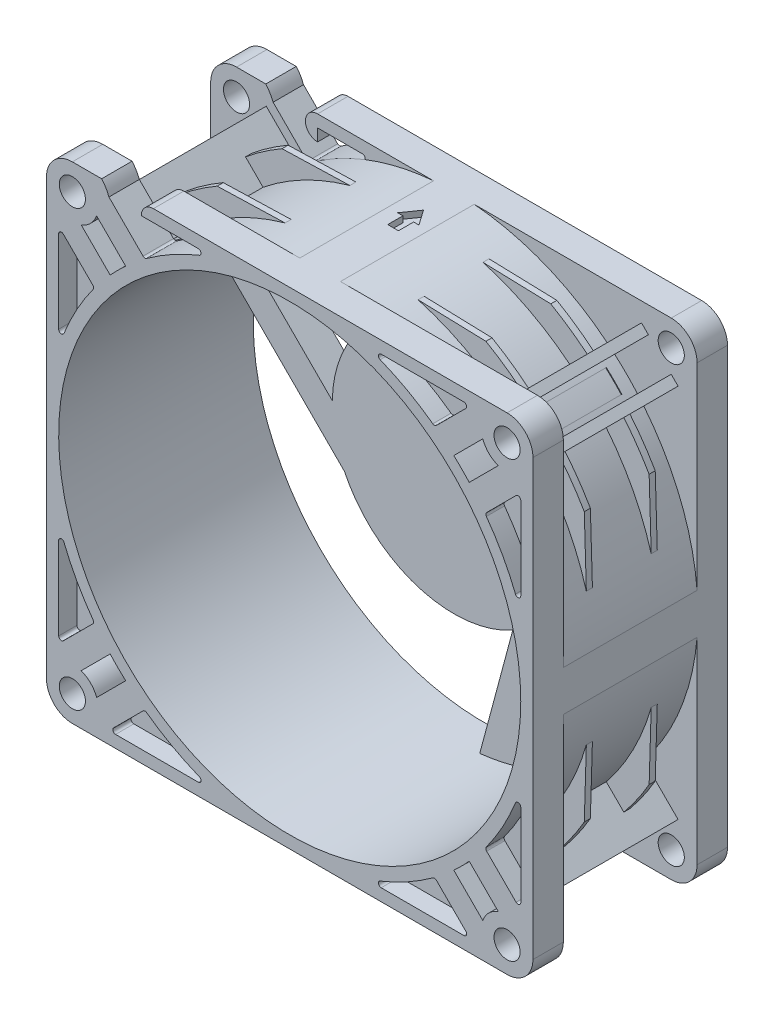
SolidWorks part; units mm, degrees
material "PW100:Mi:0:3:C1:0:1:2:Re:26:"
ref_plane "Front" through (0, 0, 0) normal (0, 0, 1) x (1, 0, 0)
ref_plane "Top" through (0, 0, 0) normal (0, 1, 0) x (1, 0, 0)
ref_plane "Right" through (0, 0, 0) normal (1, 0, 0) x (0, 0, -1)
sketch "Support-Front" plane through (0, 0, 0) normal (0, 0, 1) x (1, 0, 0)
  line L0 (-40, 0) -> (40, 0) construction
  line L1 (0, 40) -> (0, -40) construction
  line L2 (40, -35.75) -> (40, 35.75)
  line L3 (-40, -35.75) -> (-40, 35.75)
  line L4 (35.75, 40) -> (-35.75, 40)
  line L5 (35.75, -40) -> (-35.75, -40)
  line L6 (0, 40) -> (0, 54.8081) construction
  arc A0 (40, 35.75) -> (35.75, 40) centre (35.75, 35.75) ccw
  arc A1 (-40, 35.75) -> (-35.75, 40) centre (-35.75, 35.75) cw
  arc A2 (-40, -35.75) -> (-35.75, -40) centre (-35.75, -35.75) ccw
  arc A3 (40, -35.75) -> (35.75, -40) centre (35.75, -35.75) cw
  circle A4 centre (35.75, 35.75) radius 2.15
  circle A5 centre (-35.75, 35.75) radius 2.15
  circle A6 centre (-35.75, -35.75) radius 2.15
  circle A7 centre (35.75, -35.75) radius 2.15
  circle A8 centre (0, 0) radius 38
  circle A9 centre (0, 0) radius 20
  circle A10 centre (0, 0) radius 40
  circle A11 centre (0, 0) radius 54.8081 construction
  dimension "Diam-Fixing-Hole" = 4.3
  dimension "Diam-Fan-Hole" = 76
  dimension "Diam-Fixing-Plate-Fan" = 40
  dimension "Dist-Fixing-Hole" = 71.5
  dimension "Width" = 80
sketch "Support-Right" plane through (0, 0, 0) normal (1, 0, 0) x (0, 0, -1)
  line L0 (-32, 0) -> (0, 0) construction
  line L1 (-16, 40) -> (-16, -40) construction
  line L2 (-5, 40) -> (-5, -40)
  line L3 (-32, 40) -> (0, 40)
  line L4 (-32, 40) -> (-32, -40)
  line L5 (-32, -40) -> (0, -40)
  line L6 (0, 40) -> (0, -40)
  line L7 (-27, 40) -> (-27, -40)
  line L8 (-16, 40) -> (-16, 40.2793) construction
  line L9 (0, 0) -> (-2.5, 0) construction
  line L10 (-2.5, 0) -> (-5, 0) construction
  line L11 (0, 40.2793) -> (-10.6667, 40.2793) construction
  line L12 (-10.6667, 40.2793) -> (-21.3333, 40.2793) construction
  line L13 (-21.3333, 40.2793) -> (-32, 40.2793) construction
  line L14 (0, 40) -> (-16, 40.2793) construction
  dimension "D1" = 1
  dimension "Thickness" = 32
  dimension "D2" = 22
  dimension "Thickness-Flange" = 5
sketch "Support-Front-Reinforcment-Place" plane through (0, 0, 0) normal (0, 0, 1) x (1, 0, 0)
  line L0 (0, 40) -> (0, 0) construction
  line L1 (0, 38) -> (0, 40) construction
  line L2 (12.612, 40) -> (13.3947, 35.561)
  line L3 (35.75, 40) -> (-35.75, 40) construction
  line L4 (-12.612, 40) -> (-13.3947, 35.561)
  line L5 (12.612, 40) -> (0, 0) construction
  line L6 (-12.612, 40) -> (0, 0) construction
  line L7 (12.612, 40) -> (-12.612, 40)
  circle A3 centre (0, 0) radius 38 construction
  arc A4 (13.3947, 35.561) -> (-13.3947, 35.561) centre (0, 0) ccw
  point P10 (0, 39)
  dimension "D1" = 20
  dimension "D2" = 35
sketch "Support-Front-Reinforcment-Strip" plane through (0, 0, 0) normal (0, 0, 1) x (1, 0, 0)
  line L0 (25.119, 31.1294) -> (32.7448, 38.7552)
  line L1 (31.1294, 25.119) -> (38.7552, 32.7448)
  line L2 (35.75, 35.75) -> (0, 0) construction
  line L3 (29.5285, 26.9827) -> (34.3006, 31.7548)
  line L4 (33.4494, 32.1765) -> (28.9136, 27.6406)
  line L5 (35.7435, 31.9896) -> (30.0989, 26.345)
  line L6 (31.9896, 35.7435) -> (26.345, 30.0989)
  line L7 (35.75, 35.75) -> (30.0989, 26.345) construction
  line L8 (35.75, 35.75) -> (26.345, 30.0989) construction
  line L9 (38, 29.7331) -> (30.6837, 22.4168)
  line L10 (29.7331, 38) -> (22.4168, 30.6837)
  line L11 (38, 29.7331) -> (38, 0)
  line L12 (29.7331, 38) -> (0, 38)
  line L13 (35.7435, 31.9896) -> (36.8718, 30.8613)
  line L14 (31.9896, 35.7435) -> (30.8613, 36.8718)
  line L15 (31.9146, 29.3687) -> (31.2781, 30.0052) construction
  line L16 (29.7331, 38) -> (31.9896, 35.7435) construction
  line L17 (38, 29.7331) -> (36.8718, 30.8613) construction
  line L18 (29.0966, 37.55) -> (28.1965, 37.55) construction
  line L19 (31.2781, 30.0052) -> (30.6417, 30.6417) construction
  line L20 (28.2843, 28.2843) -> (33.4494, 32.1765) construction
  line L21 (32.1765, 33.4494) -> (27.6406, 28.9136)
  line L22 (26.9827, 29.5285) -> (31.7548, 34.3006)
  line L23 (0, 0) -> (-38, 0) construction
  line L24 (0, 0) -> (0, 40) construction
  line L25 (-38, 29.7331) -> (-38, 0)
  line L26 (-38, 29.7331) -> (-30.6837, 22.4168)
  line L27 (-38, 29.7331) -> (-40, 27.7331)
  line L28 (-40, -35.75) -> (-40, 35.75) construction
  line L29 (-38, -29.7331) -> (-40, -27.7331)
  line L30 (-38, -29.7331) -> (-30.6837, -22.4168)
  line L31 (-38, -29.7331) -> (-38, 0)
  line L32 (22.4168, 38) -> (22.4168, 36)
  line L33 (35.75, 40) -> (-35.75, 40) construction
  line L34 (-22.4168, 38) -> (-22.4168, 40) construction
  line L35 (22.4168, 38) -> (22.4168, 40) construction
  line L36 (-22.4168, 38) -> (-22.4168, 36)
  line L37 (0, 38) -> (-22.4168, 38)
  line L38 (-29.7331, 38) -> (-22.4168, 30.6837)
  arc A0 (32.7448, 38.7552) -> (38.7552, 32.7448) centre (35.75, 35.75) cw
  arc A1 (40, 35.75) -> (35.75, 40) centre (35.75, 35.75) ccw construction
  circle A2 centre (0, 0) radius 38
  circle A3 centre (0, 0) radius 40 construction
  arc A4 (22.4168, 36) -> (22.4168, 40) centre (22.4168, 38) ccw
  circle A5 centre (35.75, 35.75) radius 4.25
  arc A6 (31.1294, 25.119) -> (25.119, 31.1294) centre (0, 0) ccw
  circle A7 centre (0, 0) radius 38 construction
  circle A8 centre (28.6466, 37.55) radius 0.45
  circle A9 centre (23.8023, 32.7056) radius 0.45
  circle A10 centre (15.0402, 37.55) radius 0.45
  circle A11 centre (32.7056, 23.8023) radius 0.45
  circle A12 centre (37.55, 15.0402) radius 0.45
  circle A13 centre (37.55, 28.6466) radius 0.45
  circle A14 centre (35.75, 35.75) radius 6.4238
  arc A15 (-22.4168, 36) -> (-22.4168, 40) centre (-22.4168, 38) cw
  circle A16 centre (-35.75, 35.75) radius 6.4238
  circle A17 centre (-28.6466, 37.55) radius 0.45
  circle A18 centre (-23.8023, 32.7056) radius 0.45
  circle A19 centre (-15.0402, 37.55) radius 0.45
  dimension "D1" = 14
  dimension "D2" = 45
  dimension "D3" = 8
sketch "Support-Front-Bone" plane through (0, 0, 0) normal (0, 0, 1) x (1, 0, 0)
  line L0 (-19.6962, -3.473) -> (-35.8291, 12.66) construction
  line L1 (-19.9967, 0.3631) -> (-34.8294, 15.1958)
  line L2 (-18.0123, -8.6923) -> (-36.67, 9.9654)
  line L3 (0, 0) -> (0, 40) construction
  line L4 (35.75, 40) -> (-35.75, 40) construction
  line L6 (0, 0) -> (-19.6962, -3.473) construction
  circle A0 centre (0, 0) radius 38 construction
  circle A1 centre (0, 0) radius 20 construction
  arc A2 (-19.9967, 0.3631) -> (-18.0123, -8.6923) centre (0, 0) ccw
  arc A3 (-34.8294, 15.1958) -> (-36.67, 9.9654) centre (0, 0) ccw
  dimension "Angle-Bone" = 315
  dimension "Angle-Place-Bone" = 260
  dimension "Thickness-Flange" = 5
sketch "Support-Air-Exhaust" plane through (0, 0, 0) normal (0, 1, 0) x (1, 0, 0)
  line L0 (0, 0) -> (0, -10) construction
  line L1 (0, -10) -> (0, -12.5) construction
  line L2 (0, -12.5) -> (0, -15) construction
  line L3 (0, -15) -> (0, -10) construction
  line L4 (0, -10) -> (-1.7505, -12.5)
  line L5 (-1.7505, -12.5) -> (-0.8816, -12.5)
  line L6 (-0.8816, -12.5) -> (-0.8816, -15)
  line L7 (0.8816, -15) -> (-0.8816, -15)
  line L8 (0, -10) -> (-0.8816, -15) construction
  line L9 (-0.8816, -12.5) -> (0, -12.5) construction
  line L10 (0.8816, -12.5) -> (0.8816, -15)
  line L11 (1.7505, -12.5) -> (0.8816, -12.5)
  line L12 (0, -10) -> (1.7505, -12.5)
  dimension "D1" = 10
  dimension "D2" = 5
  dimension "D3" = 35
  dimension "D4" = 10
sketch "Support-Front-Extra" plane through (0, 0, 0) normal (0, 0, 1) x (1, 0, 0)
  line L1 (0, 0) -> (38.637, 10.3528) construction
  line L2 (-40, 0) -> (40, 0) construction
  line L3 (0, 0) -> (38.2818, 22.102) construction
  line L4 (35.75, 35.75) -> (0, 0) construction
  line L6 (35.75, 35.75) -> (34.2297, 34.2297) construction
  line L7 (34.2297, 34.2297) -> (31.257, 31.257) construction
  line L8 (31.257, 31.257) -> (28.2843, 28.2843) construction
  line L9 (38.2818, 22.102) -> (38.637, 10.3528)
  line L10 (22.102, 38.2818) -> (10.3528, 38.637)
  circle A4 centre (0, 0) radius 40 construction
  arc A5 (38.2818, 22.102) -> (22.102, 38.2818) centre (0, 0) ccw
  circle A6 centre (35.75, 35.75) radius 2.15 construction
  dimension "D1" = 15
  dimension "D2" = 15
ref_plane "Plane1" through (0, 0, 32) normal (0, 0, 1) x (1, 0, 0)
ref_plane "Plane2" through (0, 39, 0) normal (0, 1, 0) x (-1, 0, 0)
ref_plane "Plane3" through (0, 0, 10.6667) normal (0, 0, 1) x (1, 0, 0)
ref_plane "Plane4" through (0, 0, 21.3333) normal (0, 0, 1) x (1, 0, 0)
ref_plane "Plane5" through (0, 0, 16) normal (0, 0, 1) x (1, 0, 0)
sketch "Sketch-Body" plane through (0, 0, 0) normal (0, 0, 1) x (1, 0, 0)
  line L4 (-35.75, -40) -> (35.75, -40)
  line L5 (-40, 35.75) -> (-40, -35.75)
  line L6 (35.75, 40) -> (-35.75, 40)
  line L7 (40, -35.75) -> (40, 35.75)
  line L8 (-35.75, -40) -> (35.75, -40)
  line L9 (-40, 35.75) -> (-40, -35.75)
  line L10 (35.75, 40) -> (-35.75, 40)
  line L11 (40, -35.75) -> (40, 35.75)
  circle A0 centre (0, 0) radius 38 construction
  circle A1 centre (0, 0) radius 38
  arc A4 (-40, -35.75) -> (-35.75, -40) centre (-35.75, -35.75) ccw
  arc A5 (-35.75, 40) -> (-40, 35.75) centre (-35.75, 35.75) ccw
  arc A6 (40, 35.75) -> (35.75, 40) centre (35.75, 35.75) ccw
  arc A7 (35.75, -40) -> (40, -35.75) centre (35.75, -35.75) ccw
  arc A8 (-40, -35.75) -> (-35.75, -40) centre (-35.75, -35.75) ccw
  arc A9 (-35.75, 40) -> (-40, 35.75) centre (-35.75, 35.75) ccw
  arc A10 (40, 35.75) -> (35.75, 40) centre (35.75, 35.75) ccw
  arc A11 (35.75, -40) -> (40, -35.75) centre (35.75, -35.75) ccw
  dimension "D1" = 0
extrude "Body" add sketch "Sketch-Body" along normal up to surface (32 mm away) up to plane "Plane1"
sketch "Sketch-Cut-Body" plane through (0, 0, 0) normal (1, 0, 0) x (0, 0, -1)
  line L0 (-32, 0) -> (0, 0) construction
  line L1 (-32, 0) -> (0, 0) construction
  line L2 (-16, 40) -> (-16, 40.2793) construction
  line L5 (-27, 40.1396) -> (-27, 54.8081)
  line L6 (-27, 54.8081) -> (-5, 54.8081)
  line L7 (-27, 40.1396) -> (-5, 40.1396)
  line L9 (-5, 54.8081) -> (-5, 40.1396)
  line L10 (-5, 40) -> (-5, -40) construction
  line L11 (-27, 40) -> (-27, -40) construction
  point P9 (-16, 40.1396)
revolve "Cut-Body" cut sketch "Sketch-Cut-Body" angle 360 about L1
sketch "Sketch-Reinforcment-Strip" plane through (0, 0, 0) normal (0, 0, 1) x (1, 0, 0)
  line L0 (31.1294, 25.119) -> (38.7552, 32.7448) construction
  line L1 (25.119, 31.1294) -> (32.7448, 38.7552) construction
  line L2 (31.1294, 25.119) -> (36.8718, 30.8613)
  line L3 (25.119, 31.1294) -> (30.8613, 36.8718)
  line L4 (35.7435, 31.9896) -> (30.0989, 26.345) construction
  line L6 (35.7435, 31.9896) -> (30.0989, 26.345)
  line L7 (31.9896, 35.7435) -> (30.8613, 36.8718) construction
  line L8 (31.9896, 35.7435) -> (26.345, 30.0989) construction
  line L10 (31.9896, 35.7435) -> (26.345, 30.0989)
  line L11 (35.7435, 31.9896) -> (36.8718, 30.8613) construction
  line L12 (31.9896, 35.7435) -> (30.8613, 36.8718)
  line L13 (35.7435, 31.9896) -> (36.8718, 30.8613)
  circle A1 centre (0, 0) radius 40 construction
  arc A2 (26.345, 30.0989) -> (25.119, 31.1294) centre (0, 0) ccw
  arc A3 (31.1294, 25.119) -> (30.0989, 26.345) centre (0, 0) ccw
extrude "Reinforcment-Strip" add sketch "Sketch-Reinforcment-Strip" along normal up to surface (32 mm away) up to plane "Plane1"
pattern_circular "CirPattern-Reinforcment-Strip" count 4 over 360 about axis through (0, 0, 145.1371) along (0, 0, -1) of "Reinforcment-Strip"
sketch "Sketch-Fixing-Hole" plane through (0, 0, 0) normal (0, 0, 1) x (1, 0, 0)
  circle A0 centre (35.75, 35.75) radius 2.15 construction
  circle A1 centre (35.75, 35.75) radius 2.15
extrude "Fixing-Hole" cut sketch "Sketch-Fixing-Hole" along normal through all
pattern_circular "CirPattern-Fixing-Hole" count 4 over 360 about axis through (0, 0, 145.1371) along (0, 0, -1) of "Fixing-Hole"
sketch "Sketch-Bone" plane through (0, 0, 0) normal (0, 0, 1) x (1, 0, 0)
  line L0 (-18.0123, -8.6923) -> (-36.67, 9.9654) construction
  line L1 (-19.9967, 0.3631) -> (-34.8294, 15.1958) construction
  line L2 (-18.0123, -8.6923) -> (-36.67, 9.9654)
  line L3 (-19.9967, 0.3631) -> (-34.8294, 15.1958)
  circle A0 centre (0, 0) radius 38 construction
  circle A1 centre (0, 0) radius 20 construction
  arc A2 (-34.8294, 15.1958) -> (-36.67, 9.9654) centre (0, 0) ccw
  arc A3 (-19.9967, 0.3631) -> (-18.0123, -8.6923) centre (0, 0) ccw
extrude "Bone" add sketch "Sketch-Bone" along normal blind 5
pattern_circular "CirPattern-Bone" count 3 over 360 about axis through (0, 0, 145.1371) along (0, 0, -1) of "Bone"
sketch "Sketch1" plane through (0, 0, 32) normal (0, 0, 1) x (1, 0, 0)
  line L0 (38, 29.7331) -> (30.6837, 22.4168) construction
  line L1 (38, 29.7331) -> (38, 0) construction
  line L2 (37.2317, 28.9648) -> (32.3874, 24.1205)
  line L3 (38, 28.6466) -> (38, 15.0402)
  line L4 (29.7331, 38) -> (0, 38) construction
  line L5 (29.7331, 38) -> (22.4168, 30.6837) construction
  line L6 (28.6466, 38) -> (15.0402, 38)
  line L7 (28.9648, 37.2317) -> (24.1205, 32.3874)
  circle A1 centre (0, 0) radius 40 construction
  arc A2 (37.1322, 14.8729) -> (32.3417, 23.5374) centre (0, 0) ccw
  arc A3 (23.5374, 32.3417) -> (14.8729, 37.1322) centre (0, 0) ccw
  circle A4 centre (28.6466, 37.55) radius 0.45 construction
  circle A5 centre (15.0402, 37.55) radius 0.45 construction
  circle A6 centre (23.8023, 32.7056) radius 0.45 construction
  arc A7 (23.5374, 32.3417) -> (24.1205, 32.3874) centre (23.8023, 32.7056) ccw
  arc A8 (15.0402, 38) -> (14.8729, 37.1322) centre (15.0402, 37.55) ccw
  arc A9 (28.9648, 37.2317) -> (28.6466, 38) centre (28.6466, 37.55) ccw
  circle A10 centre (37.55, 15.0402) radius 0.45 construction
  circle A11 centre (37.55, 28.6466) radius 0.45 construction
  circle A12 centre (32.7056, 23.8023) radius 0.45 construction
  arc A13 (37.1322, 14.8729) -> (38, 15.0402) centre (37.55, 15.0402) ccw
  arc A14 (38, 28.6466) -> (37.2317, 28.9648) centre (37.55, 28.6466) ccw
  arc A15 (32.3874, 24.1205) -> (32.3417, 23.5374) centre (32.7056, 23.8023) ccw
extrude "Cut-Reinforcment-Strip-Hole-1" cut sketch "Sketch1" against normal offset from surface (3 mm away) 2 up to face at (30.9077, 30.9077, 27)
sketch "Sketch8" plane through (0, 0, 0) normal (0, 0, 1) x (1, 0, 0)
  line L0 (38, 29.7331) -> (38, 0) construction
  line L1 (38, 29.7331) -> (30.6837, 22.4168) construction
  line L2 (29.7331, 38) -> (22.4168, 30.6837) construction
  line L3 (29.7331, 38) -> (0, 38) construction
  line L4 (38, 29.7331) -> (38, 0)
  line L5 (38, 29.7331) -> (30.6837, 22.4168)
  line L6 (29.7331, 38) -> (22.4168, 30.6837)
  line L7 (29.7331, 38) -> (0, 38)
  circle A0 centre (0, 0) radius 38 construction
  arc A1 (22.4168, 30.6837) -> (0, 38) centre (0, 0) ccw
  arc A2 (38, 0) -> (30.6837, 22.4168) centre (0, 0) ccw
extrude "Cut-Reinforcment-Strip-Hole-2" [suppressed] cut sketch "Sketch8" along normal offset from surface (3 mm away) 2 up to face at (30.9077, 30.9077, 5)
sketch "Sketch5" plane through (0, 0, 10.6667) normal (0, 0, 1) x (1, 0, 0)
  line L0 (38.2818, 22.102) -> (38.637, 10.3528) construction
  line L1 (38.2818, 22.102) -> (38.637, 10.3528)
  line L6 (31.1294, 25.119) -> (38.7552, 32.7448) construction
  line L7 (25.119, 31.1294) -> (32.7448, 38.7552) construction
  line L9 (22.102, 38.2818) -> (10.3528, 38.637) construction
  line L10 (31.1294, 25.119) -> (34.1174, 28.107)
  line L11 (25.119, 31.1294) -> (28.107, 34.1174)
  line L12 (22.102, 38.2818) -> (10.3528, 38.637)
  arc A0 (28.107, 34.1174) -> (22.102, 38.2818) centre (0, 0) ccw
  arc A1 (38.637, 10.3528) -> (31.1294, 25.119) centre (0, 0) ccw
  circle A5 centre (0, 0) radius 40 construction
  arc A6 (38.2818, 22.102) -> (22.102, 38.2818) centre (0, 0) ccw construction
  arc A7 (25.119, 31.1294) -> (10.3528, 38.637) centre (0, 0) ccw
  arc A8 (38.2818, 22.102) -> (34.1174, 28.107) centre (0, 0) ccw
extrude "Extra-Support-1" add sketch "Sketch5" along normal mid plane 1
sketch "Sketch6" plane through (0, 0, 21.3333) normal (0, 0, 1) x (1, 0, 0)
  line L4 (38.2818, 22.102) -> (38.637, 10.3528) construction
  line L5 (31.1294, 25.119) -> (38.7552, 32.7448) construction
  line L6 (25.119, 31.1294) -> (32.7448, 38.7552) construction
  line L7 (22.102, 38.2818) -> (10.3528, 38.637) construction
  line L8 (38.2818, 22.102) -> (38.637, 10.3528)
  line L9 (31.1294, 25.119) -> (34.1174, 28.107)
  line L10 (25.119, 31.1294) -> (28.107, 34.1174)
  line L11 (22.102, 38.2818) -> (10.3528, 38.637)
  circle A3 centre (0, 0) radius 40 construction
  arc A4 (38.2818, 22.102) -> (22.102, 38.2818) centre (0, 0) ccw construction
  arc A5 (38.637, 10.3528) -> (31.1294, 25.119) centre (0, 0) ccw
  arc A6 (38.2818, 22.102) -> (34.1174, 28.107) centre (0, 0) ccw
  arc A7 (28.107, 34.1174) -> (22.102, 38.2818) centre (0, 0) ccw
  arc A8 (25.119, 31.1294) -> (10.3528, 38.637) centre (0, 0) ccw
extrude "Extra-Support-2" add sketch "Sketch6" along normal mid plane 1
sketch "Sketch9" plane through (0, 0, 0) normal (0, 0, 1) x (1, 0, 0)
  line L0 (26.9827, 29.5285) -> (31.7548, 34.3006) construction
  line L1 (32.1765, 33.4494) -> (27.6406, 28.9136) construction
  line L2 (33.4494, 32.1765) -> (28.9136, 27.6406) construction
  line L3 (29.5285, 26.9827) -> (34.3006, 31.7548) construction
  line L4 (25.567, 28.1128) -> (31.7548, 34.3006)
  line L5 (32.1765, 33.4494) -> (26.2261, 27.499)
  line L6 (33.4494, 32.1765) -> (27.499, 26.2261)
  line L7 (28.1128, 25.567) -> (34.3006, 31.7548)
  circle A0 centre (35.75, 35.75) radius 4.25 construction
  circle A1 centre (0, 0) radius 38 construction
  arc A2 (31.7548, 34.3006) -> (32.1765, 33.4494) centre (35.75, 35.75) ccw
  arc A3 (28.1128, 25.567) -> (27.499, 26.2261) centre (0, 0) ccw
  arc A4 (26.2261, 27.499) -> (25.567, 28.1128) centre (0, 0) ccw
  arc A5 (33.4494, 32.1765) -> (34.3006, 31.7548) centre (35.75, 35.75) ccw
extrude "Cut-Hole-1" [suppressed] cut sketch "Sketch9" along normal offset from surface (3 mm away) 2 up to face at (30.9077, 30.9077, 5)
sketch "Sketch10" plane through (0, 0, 32) normal (0, 0, 1) x (1, 0, 0)
  line L0 (26.9827, 29.5285) -> (31.7548, 34.3006) construction
  line L1 (32.1765, 33.4494) -> (27.6406, 28.9136) construction
  line L2 (33.4494, 32.1765) -> (28.9136, 27.6406) construction
  line L3 (29.5285, 26.9827) -> (34.3006, 31.7548) construction
  line L4 (26.9827, 29.5285) -> (31.7548, 34.3006)
  line L7 (29.5285, 26.9827) -> (34.3006, 31.7548)
  circle A1 centre (35.75, 35.75) radius 4.25 construction
  arc A3 (31.7548, 34.3006) -> (34.3006, 31.7548) centre (35.75, 35.75) ccw
  circle A6 centre (0, 0) radius 40 construction
  arc A7 (29.5285, 26.9827) -> (26.9827, 29.5285) centre (0, 0) ccw
extrude "Cut-Hole-2" cut sketch "Sketch10" against normal offset from surface (25 mm away) 2 up to face at (30.9077, 30.9077, 5)
pattern_circular "CirPattern" count 4 over 360 about axis through (0, 0, 145.1371) along (0, 0, -1) of "Cut-Hole-2", "Cut-Reinforcment-Strip-Hole-2", "Extra-Support-1", "Extra-Support-2", "Cut-Reinforcment-Strip-Hole-1", "Cut-Hole-1"
sketch "Sketch-Fixing-Plate-Fan" plane through (0, 0, 0) normal (0, 0, 1) x (1, 0, 0)
  circle A0 centre (0, 0) radius 20 construction
  circle A1 centre (0, 0) radius 20
extrude "Fixing-Plate-Fan" add sketch "Sketch-Fixing-Plate-Fan" along normal blind 5
sketch "Sketch4" plane through (0, 39, 0) normal (0, 1, 0) x (-1, 0, 0)
  line L7 (0.8816, 15) -> (-0.8816, 15)
  line L8 (0.8816, 12.5) -> (0.8816, 15)
  line L9 (1.7505, 12.5) -> (0.8816, 12.5)
  line L10 (0, 10) -> (1.7505, 12.5)
  line L11 (-1.7505, 12.5) -> (0, 10)
  line L12 (-0.8816, 12.5) -> (-1.7505, 12.5)
  line L13 (-0.8816, 15) -> (-0.8816, 12.5)
  line L14 (0.8816, 15) -> (-0.8816, 15)
  line L15 (0.8816, 12.5) -> (0.8816, 15)
  line L16 (1.7505, 12.5) -> (0.8816, 12.5)
  line L17 (0, 10) -> (1.7505, 12.5)
  line L18 (-1.7505, 12.5) -> (0, 10)
  line L19 (-0.8816, 12.5) -> (-1.7505, 12.5)
  line L20 (-0.8816, 15) -> (-0.8816, 12.5)
  dimension "D1" = 0
extrude "Air-Exhaust" cut sketch "Sketch4" along normal through all
sketch "Sketch12" plane through (0, 0, 0) normal (0, 0, 1) x (1, 0, 0)
  line L0 (-29.7331, 38) -> (-22.4168, 30.6837) construction
  line L2 (-22.4168, 38) -> (-22.4168, 36) construction
  line L3 (0, 38) -> (-22.4168, 38) construction
  line L4 (-29.7331, 38) -> (-24.1205, 32.3874)
  line L6 (-22.4168, 38) -> (-22.4168, 36)
  line L7 (-15.0402, 38) -> (-22.4168, 38)
  line L8 (-22.4168, 40) -> (-30.933, 40)
  circle A0 centre (0, 0) radius 40 construction
  circle A1 centre (-23.8023, 32.7056) radius 0.45 construction
  circle A2 centre (-35.75, 35.75) radius 6.4238 construction
  arc A3 (-22.4168, 40) -> (-22.4168, 36) centre (-22.4168, 38) ccw construction
  arc A4 (-14.8729, 37.1322) -> (-23.5374, 32.3417) centre (0, 0) ccw
  arc A5 (-24.1205, 32.3874) -> (-23.5374, 32.3417) centre (-23.8023, 32.7056) ccw
  arc A6 (-29.7331, 38) -> (-30.933, 40) centre (-35.75, 35.75) ccw
  arc A7 (-22.4168, 40) -> (-22.4168, 36) centre (-22.4168, 38) ccw
  circle A8 centre (-15.0402, 37.55) radius 0.45 construction
  arc A9 (-14.8729, 37.1322) -> (-15.0402, 38) centre (-15.0402, 37.55) ccw
extrude "Cut-Cable1" cut sketch "Sketch12" along normal up to surface (5 mm away) up to face at (-30.9077, 30.9077, 5)
sketch "Sketch11" plane through (0, 0, 32) normal (0, 0, 1) x (1, 0, 0)
  line L1 (-29.7331, 38) -> (-22.4168, 30.6837) construction
  line L2 (0, 38) -> (-22.4168, 38) construction
  line L3 (35.75, 40) -> (-35.75, 40) construction
  line L4 (-29.7331, 38) -> (-24.1205, 32.3874)
  line L5 (-15.0402, 38) -> (-22.4168, 38)
  line L6 (-22.4168, 38) -> (-22.4168, 36) construction
  line L7 (-22.4168, 38) -> (-22.4168, 36)
  line L8 (-22.4168, 40) -> (-30.933, 40)
  circle A0 centre (-35.75, 35.75) radius 6.4238 construction
  circle A1 centre (-23.8023, 32.7056) radius 0.45 construction
  circle A2 centre (0, 0) radius 40 construction
  circle A3 centre (-15.0402, 37.55) radius 0.45 construction
  arc A4 (-29.7331, 38) -> (-30.933, 40) centre (-35.75, 35.75) ccw
  arc A5 (-24.1205, 32.3874) -> (-23.5374, 32.3417) centre (-23.8023, 32.7056) ccw
  arc A6 (-14.8729, 37.1322) -> (-23.5374, 32.3417) centre (0, 0) ccw
  arc A7 (-14.8729, 37.1322) -> (-15.0402, 38) centre (-15.0402, 37.55) ccw
  arc A8 (-22.4168, 40) -> (-22.4168, 36) centre (-22.4168, 38) ccw construction
  arc A9 (-22.4168, 40) -> (-22.4168, 36) centre (-22.4168, 38) ccw
extrude "Cut-Cable2" cut sketch "Sketch11" against normal up to surface (5 mm away) up to face at (-30.8322, 30.8322, 27)
equation "\"Diam-Fan-Hole@Support-Front\" = \"Width@Support-Front\"-4"
